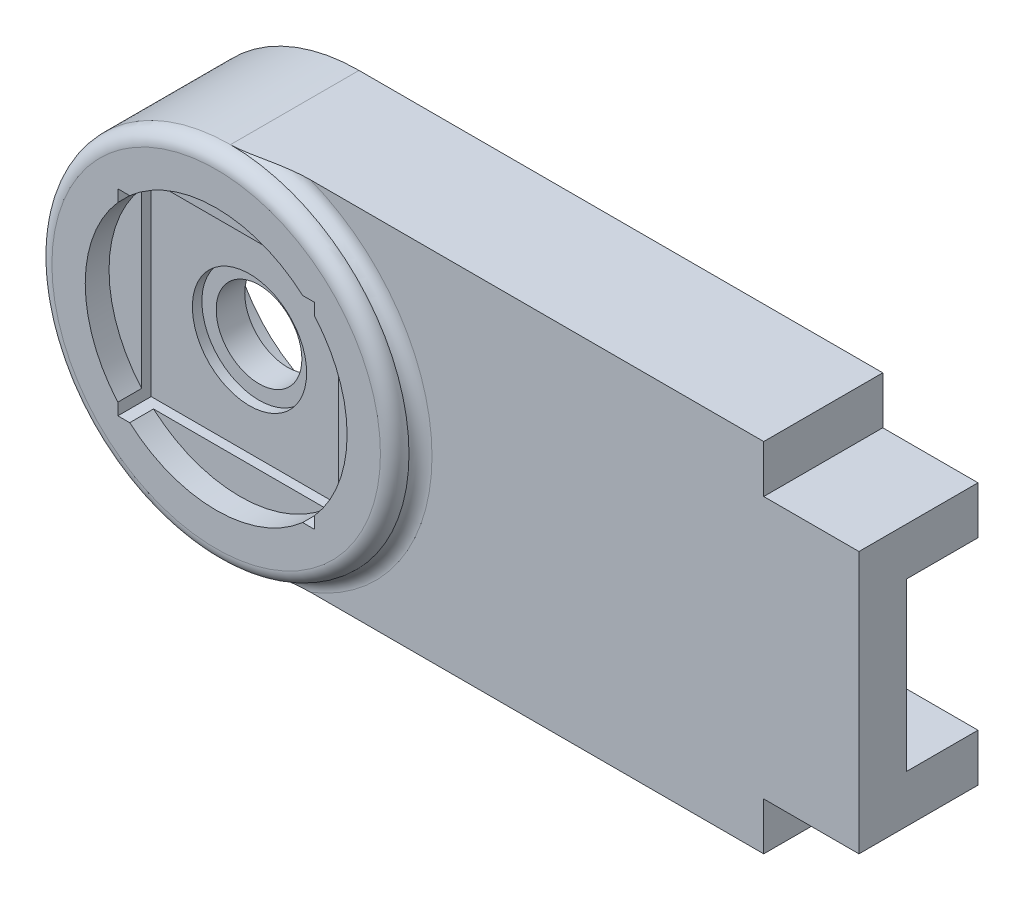
SolidWorks part; units mm, degrees
ref_plane "Спереди" through (0, 0, 0) normal (0, 0, 1) x (1, 0, 0)
ref_plane "Сверху" through (0, 0, 0) normal (0, 1, 0) x (1, 0, 0)
ref_plane "Справа" through (0, 0, 0) normal (1, 0, 0) x (0, 0, -1)
sketch "Эскиз1" plane through (0, 0, 0) normal (0, 0, 1) x (1, 0, 0)
  line L0 (0, 27.5) -> (130, 27.5)
  line L1 (0, -27.5) -> (130, -27.5)
  line L2 (130, -27.5) -> (130, 27.5)
  line L3 (0, 37.5) -> (110, 37.5)
  line L4 (110, 37.5) -> (110, 27.5)
  line L5 (0, -37.5) -> (110, -37.5)
  line L6 (110, -37.5) -> (110, -27.5)
  circle A0 centre (0, 0) radius 27.5
  circle A1 centre (0, 0) radius 37.5
  dimension "D2" = 55
  dimension "D3" = 10
  dimension "D1" = 130
  dimension "D4" = 20
  dimension "D5" = 20
extrude "Бобышка-Вытянуть1" add sketch "Эскиз1" along normal blind 25 contours A1 L1 L2 L0 | A0 | L1 A1 L0 A0 | L0 A1 L1 A0 | A1 L0 L4 L3 | A1 L5 L6 L1
sketch "Эскиз3" plane through (0, 0, 0) normal (0, 0, -1) x (-1, 0, 0)
  line L0 (0, 17.5) -> (-130, 17.5)
  line L1 (-130, -27.5) -> (-130, 27.5) construction
  line L2 (0, -17.5) -> (-130, -17.5)
  line L3 (-130, 17.5) -> (-130, -17.5)
  line L4 (-93.2785, 17.5) -> (-93.2785, 27.5)
  line L5 (-93.2785, 27.5) -> (0, 27.5)
  line L6 (-93.2785, -17.5) -> (-93.2785, -27.5)
  line L7 (-93.2785, -27.5) -> (0, -27.5)
  circle A0 centre (0, 0) radius 17.5
  arc A1 (0, -37.5) -> (0, 37.5) centre (0, 0) ccw construction
  circle A2 centre (0, 0) radius 27.5
  line M4 (-130, 27.5) -> (-130, -27.5)
  dimension "D1" = 20
  dimension "D2" = 10
extrude "Вырез-Вытянуть2" cut sketch "Эскиз3" against normal blind 15 contours A0 | A0 L0 L2 M4 | A2 L0 A0 L2 | A2 L5 L4 L0 | L0 A2 L2 A0 | A2 L2 L6 L7
sketch "Эскиз5" plane through (0, 0, 25) normal (0, 0, 1) x (1, 0, 0)
  circle A0 centre (0, 0) radius 27.5
  circle A1 centre (0, 0) radius 37.5
  dimension "D1" = 55
extrude "Бобышка-Вытянуть2" add sketch "Эскиз5" along normal blind 5
sketch "Эскиз10" plane through (0, 0, 25) normal (0, 0, 1) x (1, 0, 0)
  line L1 (-20.65, -20.65) -> (20.65, -20.65)
  line L2 (-20.65, -20.65) -> (-20.65, 20.65)
  line L3 (-20.65, 20.65) -> (20.65, 20.65)
  line L4 (20.65, -20.65) -> (20.65, 20.65)
  line L5 (-20.65, -20.65) -> (20.65, 20.65) construction
  line L6 (-20.65, 20.65) -> (20.65, -20.65) construction
  point P0 (0, 0)
  dimension "D1" = 41.3
  dimension "D2" = 41.3
extrude "Вырез-Вытянуть3" cut sketch "Эскиз10" against normal blind 2 and the other way blind 5
sketch "Эскиз11" plane through (0, 0, 23) normal (0, 0, 1) x (1, 0, 0)
  circle A0 centre (0, 0) radius 12
  dimension "D1" = 24
extrude "Вырез-Вытянуть4" cut sketch "Эскиз11" against normal blind 2
sketch "Эскиз12" plane through (0, 0, 21) normal (0, 0, 1) x (1, 0, 0)
  circle A0 centre (0, 0) radius 9
  dimension "D1" = 18
extrude "Вырез-Вытянуть5" cut sketch "Эскиз12" against normal through all
fillet "Скругление1" radius 3 1 edges at (37.5, 0, 30)
fillet "Скругление2" radius 3 1 edges at (37.5, 0, 25)
sketch "Эскиз8" plane through (0, 0, 25) normal (0, 0, 1) x (1, 0, 0)
  circle A0 centre (0, 0) radius 4
  dimension "D1" = 8
